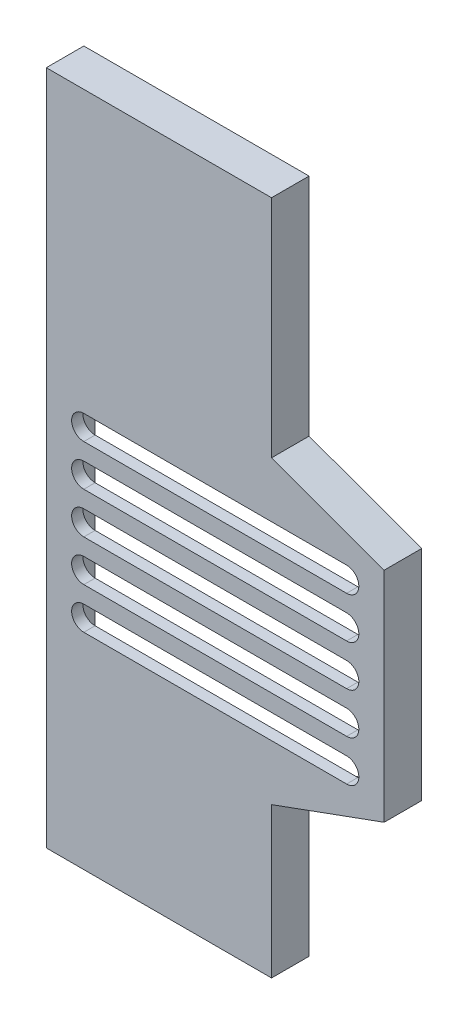
SolidWorks part; units mm, degrees
material "Сплав 2024"
ref_plane "Спереди" through (0, 0, 0) normal (0, 0, 1) x (1, 0, 0)
ref_plane "Сверху" through (0, 0, 0) normal (0, 1, 0) x (1, 0, 0)
ref_plane "Справа" through (0, 0, 0) normal (1, 0, 0) x (0, 0, -1)
sketch "Эскиз1" plane through (0, 0, 0) normal (0, 0, 1) x (1, 0, 0)
  line L0 (31.6276, -80) -> (0, -80) construction
  line L1 (0, 0) -> (60, 0)
  line L2 (0, 0) -> (0, -180)
  line L3 (0, -180) -> (60, -180)
  line L4 (60, 0) -> (60, -60)
  line L5 (30, 0) -> (30, -180) construction
  line L6 (0, -60) -> (-30, -70.9191) construction
  line L7 (-30, -70.9191) -> (-30, -129.0809) construction
  line L8 (-30, -129.0809) -> (0, -140) construction
  line L9 (0, 0) -> (0, -60) construction
  line L10 (0, -140) -> (0, -180) construction
  line L15 (60, -140) -> (60, -180)
  line L16 (90, -129.0809) -> (60, -140)
  line L17 (90, -70.9191) -> (90, -129.0809)
  line L18 (60, -60) -> (90, -70.9191)
  dimension "D1" = 40
  dimension "D2" = 180
  dimension "D3" = 80
  dimension "D4" = 60
  dimension "D5" = 60
  dimension "D6" = 90
  dimension "D7" = 110
  dimension "D8" = 110
extrude "Бобышка-Вытянуть1" add sketch "Эскиз1" along normal blind 10
fillet "Скругление1" [suppressed] radius 10
sketch "Эскиз2" plane through (0, 10, 10) normal (0, 0, 1) x (-1, 0, 0)
  line L0 (-10, 88) -> (-80, 88) construction
  line L1 (-60, 10) -> (0, 10) construction
  line L2 (-30, 190) -> (-30, 10) construction
  line L3 (-10, 102.25) -> (-80, 102.25)
  line L4 (0, 190) -> (-60, 190) construction
  line L5 (0, 10) -> (0, 190) construction
  line L6 (-10, 91.25) -> (-80, 91.25)
  line L7 (-10, 91.25) -> (-10, 84.75) construction
  line L8 (-10, 84.75) -> (-80, 84.75)
  line L9 (-10, 95.75) -> (-80, 95.75)
  line L10 (-80, 91.25) -> (-80, 84.75) construction
  line L11 (-10, 91.25) -> (-80, 84.75) construction
  line L12 (-10, 84.75) -> (-80, 91.25) construction
  line L13 (0, 10) -> (-60, 10) construction
  line L15 (-10, 113.25) -> (-80, 113.25)
  line L16 (-10, 106.75) -> (-80, 106.75)
  line L17 (-10, 124.25) -> (-80, 124.25)
  line L18 (-10, 117.75) -> (-80, 117.75)
  line L19 (-10, 135.25) -> (-80, 135.25)
  line L20 (-10, 128.75) -> (-80, 128.75)
  line L21 (-80, 138.1089) -> (-80, 88) construction
  line L23 (-90, 80.9191) -> (-90, 139.0809) construction
  arc A0 (-10, 91.25) -> (-10, 84.75) centre (-10, 88) cw
  arc A1 (-80, 91.25) -> (-80, 84.75) centre (-80, 88) ccw
  arc A2 (-80, 102.25) -> (-80, 95.75) centre (-80, 99) ccw
  arc A3 (-10, 102.25) -> (-10, 95.75) centre (-10, 99) cw
  arc A4 (-80, 113.25) -> (-80, 106.75) centre (-80, 110) ccw
  arc A5 (-10, 113.25) -> (-10, 106.75) centre (-10, 110) cw
  arc A6 (-80, 124.25) -> (-80, 117.75) centre (-80, 121) ccw
  arc A7 (-10, 124.25) -> (-10, 117.75) centre (-10, 121) cw
  arc A8 (-80, 135.25) -> (-80, 128.75) centre (-80, 132) ccw
  arc A9 (-10, 135.25) -> (-10, 128.75) centre (-10, 132) cw
  point P8 (-45, 88)
  dimension "D3" = 10
  dimension "D1" = 78
  dimension "D2" = 6.5
  dimension "D4" = 10
  dimension "D6" = 50.5
  dimension "D5" = 5
extrude "Вырез-Вытянуть1" cut sketch "Эскиз2" against normal through all
sketch "Эскиз3" plane through (0, 0, 0) normal (0, 0, -1) x (-1, 0, 0)
  line L3 (-60, -60) -> (-90, -70.9191) construction
  line L4 (-90, -70.9191) -> (-90, -129.0809) construction
  line L5 (-90, -129.0809) -> (-60, -140) construction
  line L6 (-3, -62.1006) -> (-3, -137.8994)
  line L7 (0, 0) -> (0, -180) construction
  line L8 (-57, -137.8994) -> (-3, -137.8994)
  line L9 (0, -180) -> (-60, -180) construction
  line L10 (-57, -62.1006) -> (-3, -62.1006)
  line L11 (0, 0) -> (-60, 0) construction
  line L141 (-87, -73.0197) -> (-87, -126.9803)
  line L142 (-87, -126.9803) -> (-57, -137.8994)
  line L143 (-57, -62.1006) -> (-87, -73.0197)
  dimension "D2" = 3
  dimension "D1" = 3
  dimension "D3" = 3
  dimension "D4" = 3
  dimension "D7" = 42.1006
  dimension "D8" = 62.1006
extrude "Вырез-Вытянуть2" cut sketch "Эскиз3" against normal blind 7
sketch "Эскиз4" plane through (0, 0, 0) normal (0, 0, -1) x (-1, 0, 0)
  line L0 (-30, 0) -> (-30, -180) construction
  line L1 (-40.1, -15) -> (-19.9, -15)
  line L2 (-40.1, -15) -> (-40.1, -64.75)
  line L3 (-40.1, -64.75) -> (-19.9, -64.75)
  line L4 (-19.9, -15) -> (-19.9, -64.75)
  line L5 (-40.1, -15) -> (-19.9, -64.75) construction
  line L6 (-40.1, -64.75) -> (-19.9, -15) construction
  line L7 (0, 0) -> (-60, 0) construction
  line L9 (-80, -74.75) -> (-10, -74.75) construction
  point P0 (-30, -39.875)
  dimension "D1" = 20.2
  dimension "D2" = 15
  dimension "D3" = 10
extrude "Вырез-Вытянуть3" cut sketch "Эскиз4" against normal up to surface (7 mm away) up to face at (45, -89, 7)
sketch "Эскиз6" plane through (0, 0, 0) normal (0, 0, -1) x (-1, 0, 0)
  line L0 (-60, -140) -> (-60, -180) construction
  line L1 (-57, -135) -> (-50.7, -135) construction
  line L2 (-57, -135) -> (-57, -170)
  line L3 (-57, -170) -> (-50.7, -170) construction
  line L4 (-50.7, -135) -> (-50.7, -170)
  line L5 (-57, -135) -> (-50.7, -170) construction
  line L6 (-57, -170) -> (-50.7, -135) construction
  line L7 (0, -180) -> (-60, -180) construction
  line L8 (-47.46, -135) -> (-47.46, -170)
  line L9 (-41.16, -135) -> (-41.16, -170)
  line L10 (-47.46, -135) -> (-41.16, -135) construction
  line L11 (-47.46, -170) -> (-41.16, -170) construction
  line L12 (-47.46, -135) -> (-41.16, -170) construction
  line L13 (-37.92, -135) -> (-37.92, -170)
  line L14 (-31.62, -135) -> (-31.62, -170)
  line L15 (-37.92, -135) -> (-31.62, -135) construction
  line L16 (-37.92, -170) -> (-31.62, -170) construction
  line L17 (-37.92, -135) -> (-31.62, -170) construction
  line L18 (-28.38, -135) -> (-28.38, -170)
  line L19 (-22.08, -135) -> (-22.08, -170)
  line L20 (-28.38, -135) -> (-22.08, -135) construction
  line L21 (-28.38, -170) -> (-22.08, -170) construction
  line L22 (-28.38, -135) -> (-22.08, -170) construction
  line L23 (-18.84, -135) -> (-18.84, -170)
  line L24 (-12.54, -135) -> (-12.54, -170)
  line L25 (-18.84, -135) -> (-12.54, -135) construction
  line L26 (-18.84, -170) -> (-12.54, -170) construction
  line L27 (-18.84, -135) -> (-12.54, -170) construction
  line L28 (-9.3, -135) -> (-9.3, -170)
  line L29 (-3, -135) -> (-3, -170)
  line L30 (-9.3, -135) -> (-3, -135) construction
  line L31 (-9.3, -170) -> (-3, -170) construction
  line L32 (-9.3, -135) -> (-3, -170) construction
  line L33 (0, -140) -> (0, -180) construction
  line L34 (-6.15, -170) -> (-53.85, -170) construction
  arc A0 (-50.7, -135) -> (-57, -135) centre (-53.85, -135) ccw
  arc A1 (-50.7, -170) -> (-57, -170) centre (-53.85, -170) cw
  arc A2 (-41.16, -135) -> (-47.46, -135) centre (-44.31, -135) ccw
  arc A3 (-41.16, -170) -> (-47.46, -170) centre (-44.31, -170) cw
  arc A4 (-31.62, -135) -> (-37.92, -135) centre (-34.77, -135) ccw
  arc A5 (-31.62, -170) -> (-37.92, -170) centre (-34.77, -170) cw
  arc A6 (-22.08, -135) -> (-28.38, -135) centre (-25.23, -135) ccw
  arc A7 (-22.08, -170) -> (-28.38, -170) centre (-25.23, -170) cw
  arc A8 (-12.54, -135) -> (-18.84, -135) centre (-15.69, -135) ccw
  arc A9 (-12.54, -170) -> (-18.84, -170) centre (-15.69, -170) cw
  arc A10 (-3, -135) -> (-9.3, -135) centre (-6.15, -135) ccw
  arc A11 (-3, -170) -> (-9.3, -170) centre (-6.15, -170) cw
  point P0 (-53.85, -152.5)
  point P12 (-44.31, -152.5)
  point P19 (-34.77, -152.5)
  point P26 (-25.23, -152.5)
  point P33 (-15.69, -152.5)
  point P40 (-6.15, -152.5)
  dimension "D1" = 6.3
  dimension "D2" = 35
  dimension "D3" = 3
  dimension "D4" = 10
  dimension "D6" = 3
  dimension "D5" = 6
extrude "Вырез-Вытянуть4" cut sketch "Эскиз6" against normal up to surface (7 mm away) up to face at (41.4, -75.4201, 7)
equation "\"D6@Эскиз1\"=\"D5@Эскиз1\"+30"
